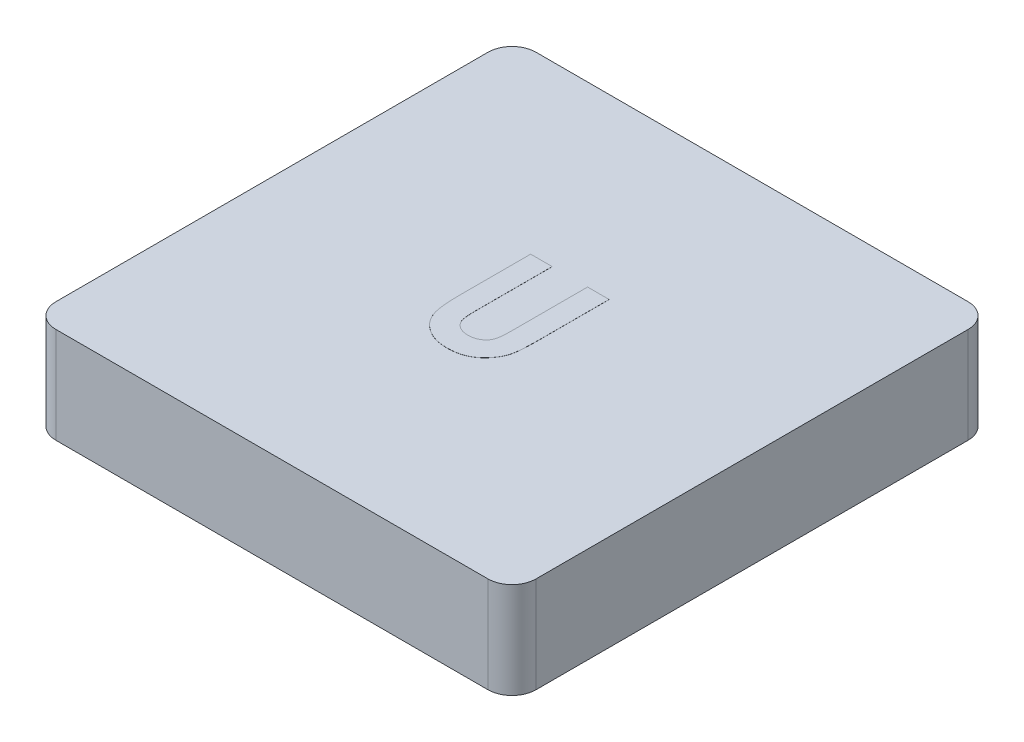
SolidWorks part; units mm, degrees
ref_plane "Front Plane" through (0, 0, 0) normal (0, 0, 1) x (1, 0, 0)
ref_plane "Top Plane" through (0, 0, 0) normal (0, 1, 0) x (1, 0, 0)
ref_plane "Right Plane" through (0, 0, 0) normal (1, 0, 0) x (0, 0, -1)
sketch "Sketch1" plane through (0, 0, 0) normal (0, 1, 0) x (1, 0, 0)
  line L0 (0, 0) -> (12.7, 0)
  line L1 (12.7, 0) -> (12.7, 12.7)
  line L2 (12.7, 12.7) -> (0, 12.7)
  line L3 (0, 12.7) -> (0, 0)
  dimension "D1" = 12.7
  dimension "D2" = 12.7
extrude "Boss-Extrude1" add sketch "Sketch1" along normal blind 2.54
fillet "Fillet1" radius 0.635 4 edges at (0, 1.27, -12.7) (12.7, 1.27, -12.7) (12.7, 1.27, 0) (0, 1.27, 0)
shell "Shell1" thickness 0.635 removed face at (6.35, 0, -6.35)
sketch "Sketch2" plane through (0, 1.905, 0) normal (0, -1, 0) x (-1, 0, 0)
  line L0 (-0.635, 6.35) -> (-12.065, 6.35) construction
  line L1 (-0.635, 12.065) -> (-0.635, 0.635) construction
  line L2 (-12.065, 0.635) -> (-12.065, 12.065) construction
  line L3 (-6.35, 0.635) -> (-6.35, 12.065) construction
  line L4 (-0.635, 0.635) -> (-12.065, 0.635) construction
  line L5 (-12.065, 12.065) -> (-0.635, 12.065) construction
  circle A0 centre (-6.35, 6.35) radius 2.54
  dimension "D1" = 5.08
extrude "Boss-Extrude2" add sketch "Sketch2" along normal up to surface (1.905 mm away) up to face at (6.35, 0, -6.35)
sketch "Sketch3" plane through (0, 2.54, 0) normal (0, 1, 0) x (1, 0, 0)
  line L0 (0, 12.065) -> (0, 0.635) construction
  line L1 (0.635, 0) -> (12.065, 0) construction
  text T0 "<b>U</b>"
  point P1 (0, 0)
  dimension "D1" = 4.826
  dimension "D2" = 4.826
extrude "Boss-Extrude3" add sketch "Sketch3" along normal blind 0.0025
